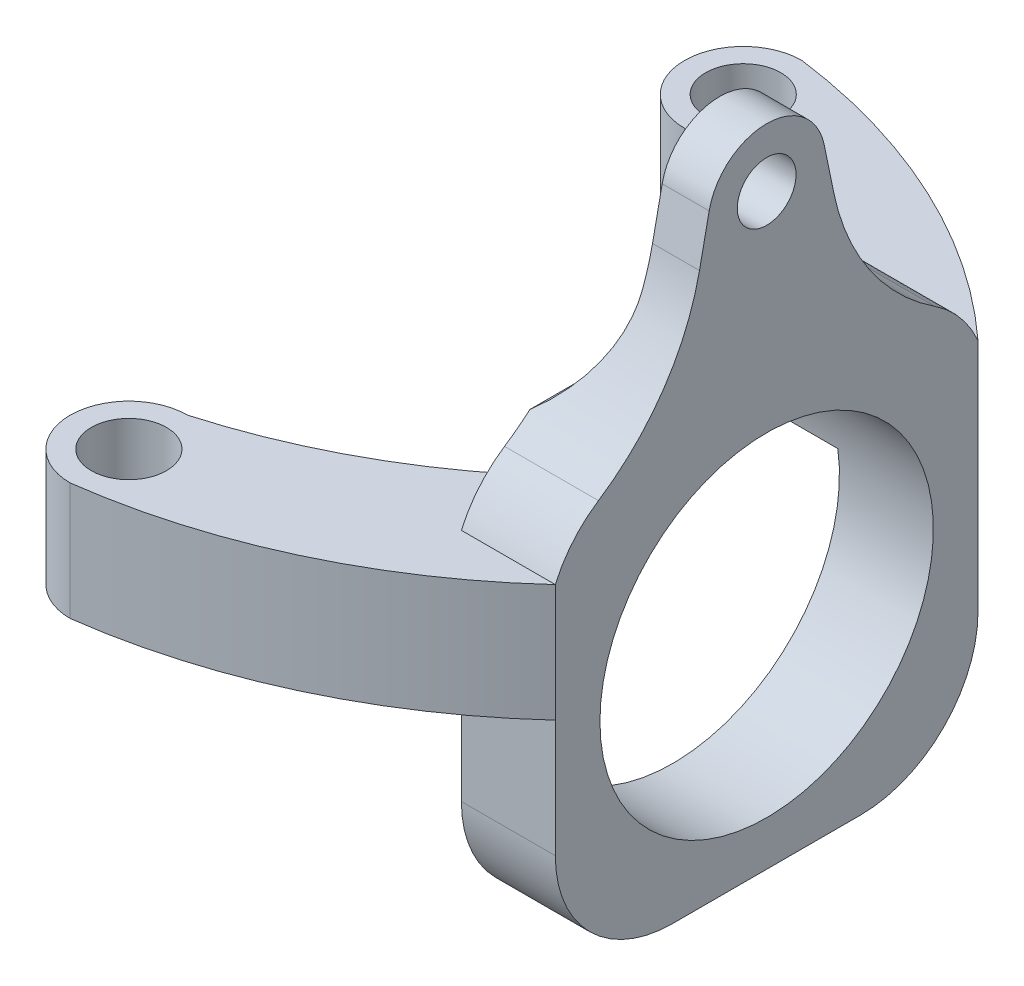
SolidWorks part; units mm, degrees
ref_plane "Front Plane" through (0, 0, 0) normal (0, 0, 1) x (1, 0, 0)
ref_plane "Top Plane" through (0, 0, 0) normal (0, 1, 0) x (1, 0, 0)
ref_plane "Right Plane" through (0, 0, 0) normal (1, 0, 0) x (0, 0, -1)
sketch "Sketch1" plane through (0, 0, 0) normal (0, 1, 0) x (1, 0, 0)
  line L0 (0, 0) -> (14.8492, -14.8492) construction
  line L1 (-13.0815, -13.0815) -> (13.0815, -13.0815) construction
  line L2 (-13.0815, -13.0815) -> (-13.0815, 13.0815) construction
  line L3 (-13.0815, 13.0815) -> (13.0815, 13.0815) construction
  line L4 (13.0815, -13.0815) -> (13.0815, 13.0815) construction
  line L5 (-13.0815, -13.0815) -> (13.0815, 13.0815) construction
  line L6 (-13.0815, 13.0815) -> (13.0815, -13.0815) construction
  line L7 (0, 0) -> (14.8492, 14.8492) construction
  line L8 (0, 0) -> (21, 0) construction
  line L21 (23.16, -9) -> (27.16, -9)
  line L22 (23.16, -9) -> (23.16, 9)
  line L23 (23.16, 9) -> (27.16, 9)
  line L24 (27.16, -9) -> (27.16, 9)
  line L25 (23.16, -9) -> (27.16, 9) construction
  line L26 (23.16, 9) -> (27.16, -9) construction
  circle A0 centre (0, 0) radius 18.5 construction
  circle A1 centre (0, 0) radius 15.5 construction
  circle A2 centre (13.0815, 13.0815) radius 1.6
  circle A3 centre (13.0815, -13.0815) radius 1.6
  circle A5 centre (13.0815, 13.0815) radius 2.5 construction
  circle A6 centre (13.0815, -13.0815) radius 2.5 construction
  circle A7 centre (0, 0) radius 21 construction
  arc A8 (14.7258, 11.1983) -> (14.7258, -11.1983) centre (0, 0) cw construction
  arc A9 (13.0815, 10.5815) -> (13.0815, 15.5815) centre (13.0815, 13.0815) cw
  arc A10 (13.0815, -10.5815) -> (13.7986, -15.4764) centre (13.0815, -13.0815) ccw
  arc A11 (13.0815, -15.5815) -> (27.16, -9) centre (9.7002, 10) ccw
  arc A12 (13.0815, 15.5815) -> (27.16, 9) centre (9.7002, -10) cw
  arc A13 (13.0815, -10.5815) -> (23.16, -5) centre (6.0463, 14.0121) ccw
  arc A15 (13.0815, 10.5815) -> (23.16, 5) centre (6.0463, -14.0121) cw
  point P18 (14.8492, 14.8492)
  point P19 (14.8492, -14.8492)
  point P20 (20.1632, -5.8689)
  point P21 (18.1632, 0)
  point P32 (20.1632, 5.8689)
  point P33 (25.16, 0)
  dimension "D1" = 31
  dimension "D2" = 37
  dimension "D3" = 3.2
  dimension "D4" = 3.2
  dimension "D5" = 5
  dimension "D6" = 5
  dimension "D14" = 25.58
  dimension "D16" = 25.58
  dimension "D17" = 2.5
  dimension "D18" = 2.5
  dimension "D7" = 10
  dimension "D8" = 10
  dimension "D9" = 18
  dimension "D10" = 9
  dimension "D11" = 23.16
  dimension "D12" = 4
  dimension "D13" = 5
  dimension "D15" = 5
extrude "Boss-Extrude1" add sketch "Sketch1" along normal blind 5 contours A9 A10 A3 A2 | L21 L24 L23 L22 | A9 A15 L22 L23 A12 A2 region at (25.16, 0, 0) region at (18.6918, 0, 11.0655) region at (18.6918, 0, -11.0655)
sketch "Sketch2" plane through (0, 5, 0) normal (0, 1, 0) x (1, 0, 0)
  line L0 (27.16, -9) -> (27.16, 9) construction
  line L1 (27.16, 9) -> (23.16, 9)
  line L2 (27.16, 9) -> (27.16, -9)
  line L3 (27.16, -9) -> (23.16, -9)
  line L4 (23.16, 9) -> (23.16, -9)
  dimension "D1" = 18
  dimension "D2" = 4
  dimension "D3" = 9
extrude "Boss-Extrude2" add sketch "Sketch2" along normal blind 3 and the other way blind 15
sketch "Sketch3" plane through (27.16, 0, 0) normal (1, 0, 0) x (0, 0, -1)
  line L1 (9, 0) -> (15.5815, 0) construction
  circle A0 centre (0, -1) radius 7.1
  dimension "D2" = 14.2
  dimension "D1" = 1
extrude "Cut-Extrude1" cut sketch "Sketch3" along normal through all and the other way through all
fillet "Fillet1" radius 5 4 edges at (25.16, -10, -9) (25.16, -10, 9) (25.16, 8, -9) (25.16, 8, 9)
sketch "Sketch4" plane through (27.16, 0, 0) normal (1, 0, 0) x (0, 0, -1)
  line L1 (-4, 8) -> (-1.8743, 18.2823) construction
  line L2 (4, 8) -> (1.9868, 17.7381) construction
  line L3 (-4, 8) -> (-2.4482, 15.5061)
  line L4 (-2.4482, 15.5061) -> (2.4482, 15.5061)
  line L5 (2.4482, 15.5061) -> (4, 8)
  line L6 (4, 8) -> (-4, 8)
  circle A0 centre (0, 15) radius 1.25
  circle A1 centre (0, 15) radius 2.5
  line M12 (4.4174, 8) -> (-4.4174, 8)
  dimension "D2" = 2.5
  dimension "D3" = 5
  dimension "D1" = 15
  dimension "D4" = 0
extrude "Boss-Extrude3" add sketch "Sketch4" against normal blind 2 contours L4 A1 A0 | L4 A1 A0 | A1 L3 L5 M12 region at (27.16, 10.5103, 0) region at (27.16, 16.4454, 0) region at (27.16, 15.4478, 1.7956)
fillet "Fillet9" radius 5 1 edges at (25.16, 8, 0)
fillet "Fillet10" radius 10 2 edges at (25.16, 8, -4) (25.16, 8, 4)
